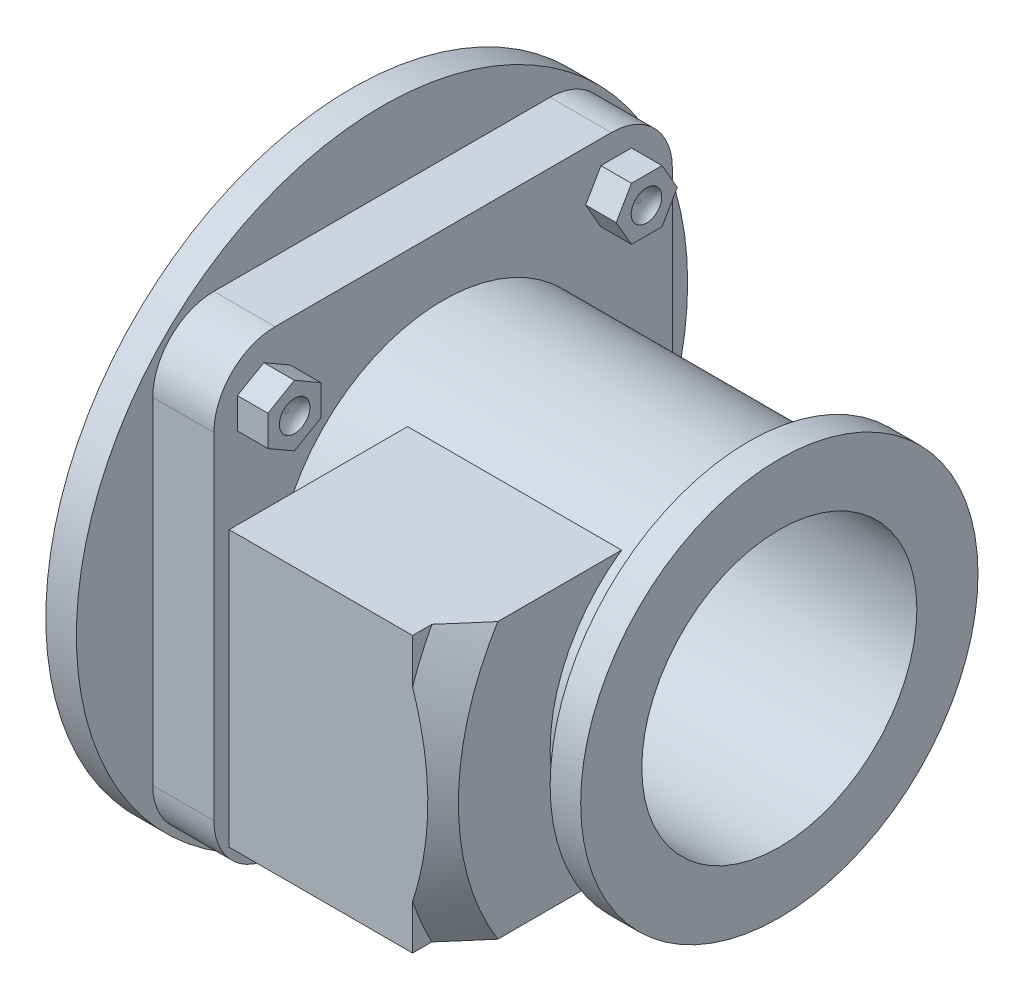
SolidWorks part; units mm, degrees
ref_plane "Front Plane" through (0, 0, 0) normal (0, 0, 1) x (1, 0, 0)
ref_plane "Top Plane" through (0, 0, 0) normal (0, 1, 0) x (1, 0, 0)
ref_plane "Right Plane" through (0, 0, 0) normal (1, 0, 0) x (0, 0, -1)
sketch "Sketch1" plane through (0, 0, 0) normal (1, 0, 0) x (0, 0, -1)
  circle A0 centre (0, 0) radius 100
  dimension "D1" = 200
extrude "Boss-Extrude1" add sketch "Sketch1" along normal blind 10
sketch "Sketch2" plane through (10, 0, 0) normal (1, 0, 0) x (0, 0, -1)
  line L1 (-75, 75) -> (75, 75)
  line L2 (-75, 75) -> (-75, -75)
  line L3 (-75, -75) -> (75, -75)
  line L4 (75, 75) -> (75, -75)
  line L5 (-75, 75) -> (75, -75) construction
  line L6 (-75, -75) -> (75, 75) construction
  point P0 (0, 0)
  dimension "D1" = 150
  dimension "D2" = 150
extrude "Boss-Extrude2" add sketch "Sketch2" along normal blind 20
fillet "Fillet1" radius 20 4 edges at (20, 75, 75) (20, -75, 75) (20, -75, -75) (20, 75, -75)
sketch "Sketch3" plane through (30, 0, 0) normal (1, 0, 0) x (0, 0, -1)
  circle A0 centre (0, 0) radius 55
  dimension "D1" = 110
extrude "Boss-Extrude3" add sketch "Sketch3" along normal blind 100
sketch "Sketch4" plane through (130, 0, 0) normal (1, 0, 0) x (0, 0, -1)
  circle A0 centre (0, 0) radius 65
  dimension "D1" = 130
extrude "Boss-Extrude4" add sketch "Sketch4" along normal blind 10
sketch "Sketch5" plane through (0, 0, 0) normal (0, 0, 1) x (1, 0, 0)
  line L0 (-7.971, 0) -> (199.7009, 0) construction
  line L1 (30, 55) -> (30, -55) construction
  line L2 (50, 45) -> (120, 45)
  line L3 (50, 45) -> (50, -45)
  line L4 (50, -45) -> (120, -45)
  line L5 (120, 45) -> (120, -45)
  line L6 (50, 45) -> (120, -45) construction
  line L7 (50, -45) -> (120, 45) construction
  point P3 (85, 0)
  dimension "D1" = 70
  dimension "D2" = 20
  dimension "D3" = 90
extrude "Boss-Extrude5" add sketch "Sketch5" along normal blind 90
sketch "Sketch6" plane through (120, 0, 0) normal (1, 0, 0) x (0, 0, -1)
  line L3 (-90, -45) -> (-31.6228, -45)
  line L4 (-31.6228, 45) -> (-90, 45)
  line L5 (-90, 45) -> (-90, -45)
  line L6 (-90, -45) -> (-72.111, -45)
  line L7 (-72.111, 45) -> (-90, 45)
  line L8 (-90, 45) -> (-90, -45)
  arc A0 (-72.111, 45) -> (-72.111, -45) centre (0, 0) ccw
  arc A2 (-31.6228, 45) -> (-31.6228, -45) centre (0, 0) ccw
  dimension "D1" = 170
  dimension "D2" = 0
extrude "Cut-Extrude1" cut sketch "Sketch6" against normal blind 10
chamfer "Chamfer1" distance 10 angle 45 1 edges at (110, 0, 85)
sketch "Sketch7" plane through (140, 0, 0) normal (1, 0, 0) x (0, 0, -1)
  circle A0 centre (0, 0) radius 45
  dimension "D1" = 90
extrude "Cut-Extrude2" cut sketch "Sketch7" against normal blind 100
sketch "Sketch8" plane through (30, 0, 0) normal (1, 0, 0) x (0, 0, -1)
  line L0 (75, -55) -> (75, 55) construction
  line L1 (67.3205, -61.6274) -> (67.3205, -51.6274)
  line L2 (67.3205, -51.6274) -> (58.6603, -46.6274)
  line L3 (58.6603, -46.6274) -> (50, -51.6274)
  line L4 (50, -51.6274) -> (50, -61.6274)
  line L5 (50, -61.6274) -> (58.6603, -66.6274)
  line L6 (58.6603, -66.6274) -> (67.3205, -61.6274)
  line L7 (75, -55) -> (75, 55) construction
  circle A0 centre (58.6603, -56.6274) radius 8.6603 construction
  dimension "D1" = 10
  dimension "D2" = 25
extrude "Boss-Extrude6" add sketch "Sketch8" along normal blind 10
sketch "Sketch9" plane through (40, 0, 0) normal (1, 0, 0) x (0, 0, -1)
  circle A0 centre (58.5882, -56.5253) radius 5
  dimension "D1" = 10
extrude "Cut-Extrude3" cut sketch "Sketch9" against normal blind 2.5
fillet "Fillet9" radius 5 1 edges at (37.5, -56.5253, -63.5882)
pattern_circular "CirPattern1" count 4 every 90 about axis through (130, 0, 0) along (-1, 0, 0) of "Boss-Extrude6", "Cut-Extrude3", "Fillet9"
